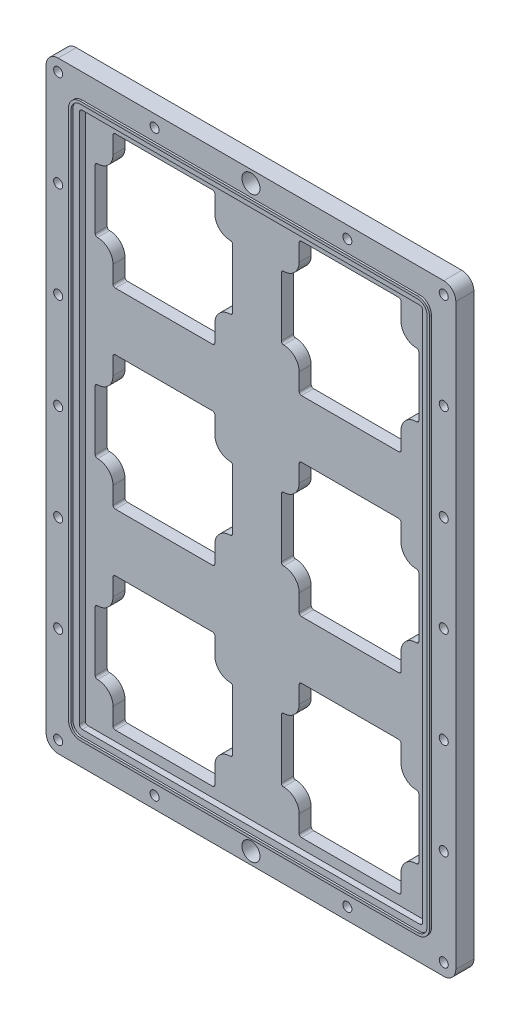
SolidWorks part; units mm, degrees
ref_plane "Front Plane" through (0, 0, 0) normal (0, 0, 1) x (1, 0, 0)
ref_plane "Top Plane" through (0, 0, 0) normal (0, 1, 0) x (1, 0, 0)
ref_plane "Right Plane" through (0, 0, 0) normal (1, 0, 0) x (0, 0, -1)
sketch "Sketch1" plane through (0, 0, 0) normal (0, 0, 1) x (1, 0, 0)
  line L1 (0, 0) -> (215.9, 0)
  line L2 (0, 0) -> (0, 317.5)
  line L3 (0, 317.5) -> (215.9, 317.5)
  line L4 (215.9, 0) -> (215.9, 317.5)
  dimension "D1" = 317.5
  dimension "D2" = 215.9
extrude "Boss-Extrude1" add sketch "Sketch1" along normal blind 9.525
sketch "Sketch4" plane through (0, 0, 9.525) normal (0, 0, 1) x (1, 0, 0)
  line L3 (0, 317.5) -> (0, 0) construction
  line L4 (6.35, 311.15) -> (209.55, 311.15) construction
  line L5 (6.35, 311.15) -> (6.35, 6.35) construction
  line L6 (6.35, 6.35) -> (209.55, 6.35) construction
  line L7 (209.55, 311.15) -> (209.55, 6.35) construction
  line L8 (215.9, 317.5) -> (0, 317.5) construction
  line L9 (215.9, 0) -> (215.9, 317.5) construction
  line L10 (0, 0) -> (215.9, 0) construction
  circle A0 centre (6.35, 6.35) radius 2.3813
  circle A1 centre (6.35, 311.15) radius 2.3813
  circle A2 centre (209.55, 311.15) radius 2.3813
  circle A3 centre (209.55, 6.35) radius 2.3813
  circle A4 centre (57.15, 311.15) radius 2.3813
  circle A5 centre (57.15, 6.35) radius 2.3812
  circle A6 centre (107.95, 311.15) radius 2.3813
  circle A7 centre (107.95, 6.35) radius 2.3813
  circle A8 centre (158.75, 311.15) radius 2.3813
  circle A9 centre (158.75, 6.35) radius 2.3813
  circle A10 centre (6.35, 260.35) radius 2.3813
  circle A11 centre (209.55, 260.35) radius 2.3813
  circle A12 centre (6.35, 209.55) radius 2.3813
  circle A13 centre (209.55, 209.55) radius 2.3813
  circle A14 centre (6.35, 158.75) radius 2.3812
  circle A15 centre (209.55, 158.75) radius 2.3813
  circle A16 centre (6.35, 107.95) radius 2.3812
  circle A17 centre (209.55, 107.95) radius 2.3813
  circle A18 centre (6.35, 57.15) radius 2.3813
  circle A19 centre (209.55, 57.15) radius 2.3813
  dimension "D5" = 4.7625
  dimension "D1" = 6.35
  dimension "D2" = 6.35
  dimension "D3" = 6.35
  dimension "D4" = 6.35
  dimension "D6" = 4
  dimension "D7" = 6
extrude "Cut-Extrude1" cut sketch "Sketch4" against normal through all
sketch "Sketch5" plane through (0, 0, 9.525) normal (0, 0, 1) x (1, 0, 0)
  line L0 (0, 317.5) -> (0, 0) construction
  line L1 (19.05, 304.8) -> (196.85, 304.8) construction
  line L2 (12.7, 298.45) -> (12.7, 19.05) construction
  line L3 (19.05, 12.7) -> (196.85, 12.7) construction
  line L4 (203.2, 298.45) -> (203.2, 19.05) construction
  line L5 (215.9, 317.5) -> (0, 317.5) construction
  line L6 (215.9, 0) -> (215.9, 317.5) construction
  line L7 (0, 0) -> (215.9, 0) construction
  line L8 (19.05, 14.2875) -> (196.85, 14.2875) construction
  line L9 (14.2875, 298.45) -> (14.2875, 19.05) construction
  line L10 (19.05, 303.2125) -> (196.85, 303.2125) construction
  line L11 (201.6125, 298.45) -> (201.6125, 19.05) construction
  line L12 (12.827, 298.45) -> (12.827, 19.05)
  line L13 (19.05, 304.673) -> (196.85, 304.673)
  line L14 (203.073, 298.45) -> (203.073, 19.05)
  line L15 (19.05, 12.827) -> (196.85, 12.827)
  line L16 (201.7395, 298.45) -> (201.7395, 19.05)
  line L17 (19.05, 303.3395) -> (196.85, 303.3395)
  line L18 (14.1605, 298.45) -> (14.1605, 19.05)
  line L19 (19.05, 14.1605) -> (196.85, 14.1605)
  arc A0 (196.85, 12.7) -> (203.2, 19.05) centre (196.85, 19.05) ccw construction
  arc A1 (12.7, 19.05) -> (19.05, 12.7) centre (19.05, 19.05) ccw construction
  arc A2 (196.85, 304.8) -> (203.2, 298.45) centre (196.85, 298.45) cw construction
  arc A3 (19.05, 304.8) -> (12.7, 298.45) centre (19.05, 298.45) ccw construction
  arc A4 (14.2875, 19.05) -> (19.05, 14.2875) centre (19.05, 19.05) ccw construction
  arc A5 (19.05, 303.2125) -> (14.2875, 298.45) centre (19.05, 298.45) ccw construction
  arc A6 (196.85, 303.2125) -> (201.6125, 298.45) centre (196.85, 298.45) cw construction
  arc A7 (196.85, 14.2875) -> (201.6125, 19.05) centre (196.85, 19.05) ccw construction
  arc A8 (19.05, 304.673) -> (12.827, 298.45) centre (19.05, 298.45) ccw
  arc A9 (196.85, 304.673) -> (203.073, 298.45) centre (196.85, 298.45) cw
  arc A10 (196.85, 12.827) -> (203.073, 19.05) centre (196.85, 19.05) ccw
  arc A11 (12.827, 19.05) -> (19.05, 12.827) centre (19.05, 19.05) ccw
  arc A12 (196.85, 303.3395) -> (201.7395, 298.45) centre (196.85, 298.45) cw
  arc A13 (19.05, 303.3395) -> (14.1605, 298.45) centre (19.05, 298.45) ccw
  arc A14 (14.1605, 19.05) -> (19.05, 14.1605) centre (19.05, 19.05) ccw
  arc A15 (196.85, 14.1605) -> (201.7395, 19.05) centre (196.85, 19.05) ccw
  dimension "D5" = 6.35
  dimension "D1" = 12.7
  dimension "D2" = 12.7
  dimension "D3" = 12.7
  dimension "D4" = 12.7
  dimension "D6" = 1.5875
  dimension "D7" = 1.5875
  dimension "D8" = 0.127
  dimension "D9" = 0.127
  dimension "D10" = 0.127
sketch "Sketch6" plane through (0, 0, 9.525) normal (0, 0, 1) x (1, 0, 0)
  line L24 (196.85, 300.0375) -> (19.05, 300.0375)
  line L25 (198.4375, 19.05) -> (198.4375, 298.45)
  line L26 (19.05, 17.4625) -> (196.85, 17.4625)
  line L27 (17.4625, 298.45) -> (17.4625, 19.05)
  line L28 (196.85, 300.0375) -> (19.05, 300.0375)
  line L29 (198.4375, 19.05) -> (198.4375, 298.45)
  line L30 (19.05, 17.4625) -> (196.85, 17.4625)
  line L31 (17.4625, 298.45) -> (17.4625, 19.05)
  arc A20 (19.05, 300.0375) -> (17.4625, 298.45) centre (19.05, 298.45) ccw
  arc A21 (198.4375, 298.45) -> (196.85, 300.0375) centre (196.85, 298.45) ccw
  arc A22 (196.85, 17.4625) -> (198.4375, 19.05) centre (196.85, 19.05) ccw
  arc A23 (17.4625, 19.05) -> (19.05, 17.4625) centre (19.05, 19.05) ccw
  arc A24 (19.05, 300.0375) -> (17.4625, 298.45) centre (19.05, 298.45) ccw
  arc A25 (198.4375, 298.45) -> (196.85, 300.0375) centre (196.85, 298.45) ccw
  arc A26 (196.85, 17.4625) -> (198.4375, 19.05) centre (196.85, 19.05) ccw
  arc A27 (17.4625, 19.05) -> (19.05, 17.4625) centre (19.05, 19.05) ccw
  dimension "D1" = 3.175
extrude "Cut-Extrude3" cut sketch "Sketch6" against normal blind 3.175
extrude "Boss-Extrude2" add sketch "Sketch5" along normal blind 1.016 contours L12 A11 L15 A10 L14 A9 L13 A8 A15 L19 A14 L18 A13 L17 A12 L16 region at (14.896, 302.604, 9.525)
sketch "Sketch7" plane through (0, 0, 9.525) normal (0, 0, 1) x (1, 0, 0)
  circle A0 centre (107.95, 6.35) radius 4.7625
  circle A1 centre (107.95, 311.15) radius 4.7625
  dimension "D1" = 9.525
extrude "Cut-Extrude4" cut sketch "Sketch7" against normal through all
fillet "Fillet1" radius 6.35 4 edges at (0, 317.5, 4.7625) (215.9, 317.5, 4.7625) (0, 0, 4.7625) (215.9, 0, 4.7625)
sketch "Sketch8" plane through (0, 0, 0) normal (0, 0, -1) x (-1, 0, 0)
  line L0 (-194.818, 275.209) -> (-194.818, 244.0178)
  line L1 (-185.42, 234.6198) -> (-185.42, 225.6282)
  line L2 (-182.6006, 222.8088) -> (-131.3942, 222.8088)
  line L3 (-128.5748, 225.6282) -> (-128.5748, 234.6198)
  line L4 (-119.1768, 244.0178) -> (-119.1768, 275.209)
  line L5 (-128.5748, 284.607) -> (-128.5748, 293.5986)
  line L6 (-131.3942, 296.418) -> (-182.6006, 296.418)
  line L7 (-185.42, 293.5986) -> (-185.42, 284.607)
  line L8 (-191.9986, 296.418) -> (-191.9986, 222.8088) construction
  line L9 (-194.818, 293.5986) -> (-119.1768, 293.5986) construction
  line L10 (-194.818, 296.418) -> (-119.1768, 296.418) construction
  line L11 (-194.818, 296.418) -> (-194.818, 222.8088) construction
  line L12 (-194.818, 222.8088) -> (-119.1768, 222.8088) construction
  line L13 (-119.1768, 296.418) -> (-119.1768, 222.8088) construction
  line L14 (-194.818, 284.607) -> (-119.1768, 284.607) construction
  line L15 (-194.818, 275.209) -> (-119.1768, 275.209) construction
  line L16 (-194.818, 244.0178) -> (-119.1768, 244.0178) construction
  line L17 (-194.818, 234.6198) -> (-119.1768, 234.6198) construction
  line L18 (-194.818, 225.6282) -> (-119.1768, 225.6282) construction
  line L19 (-185.42, 222.8088) -> (-185.42, 296.418) construction
  line L20 (-182.6006, 296.418) -> (-182.6006, 222.8088) construction
  line L21 (-131.3942, 296.418) -> (-131.3942, 222.8088) construction
  line L22 (-128.5748, 296.418) -> (-128.5748, 222.8088) construction
  line L23 (-121.9962, 222.8088) -> (-121.9962, 296.418) construction
  line L24 (-119.1768, 278.0284) -> (-194.818, 278.0284) construction
  line L27 (-131.3942, 298.45) -> (-182.6006, 298.45)
  line L28 (-187.452, 293.5986) -> (-187.452, 284.607)
  line L29 (-196.85, 275.209) -> (-196.85, 244.0178)
  line L30 (-187.452, 234.6198) -> (-187.452, 225.6282)
  line L31 (-182.6006, 220.7768) -> (-131.3942, 220.7768)
  line L32 (-126.5428, 225.6282) -> (-126.5428, 234.6198)
  line L33 (-117.1448, 244.0178) -> (-117.1448, 275.209)
  line L34 (-126.5428, 284.607) -> (-126.5428, 293.5986)
  line L35 (-209.55, 317.5) -> (-6.35, 317.5) construction
  line L36 (-215.9, 6.35) -> (-215.9, 311.15) construction
  arc A0 (-191.9986, 278.0284) -> (-185.42, 284.607) centre (-191.9986, 284.607) ccw
  arc A1 (-191.9986, 278.0284) -> (-194.818, 275.209) centre (-191.9986, 275.209) ccw
  arc A2 (-194.818, 244.0178) -> (-191.9986, 241.1984) centre (-191.9986, 244.0178) ccw
  arc A3 (-185.42, 234.6198) -> (-191.9986, 241.1984) centre (-191.9986, 234.6198) ccw
  arc A4 (-185.42, 225.6282) -> (-182.6006, 222.8088) centre (-182.6006, 225.6282) ccw
  arc A5 (-131.3942, 222.8088) -> (-128.5748, 225.6282) centre (-131.3942, 225.6282) ccw
  arc A6 (-121.9962, 241.1984) -> (-128.5748, 234.6198) centre (-121.9962, 234.6198) ccw
  arc A7 (-121.9962, 241.1984) -> (-119.1768, 244.0178) centre (-121.9962, 244.0178) ccw
  arc A8 (-119.1768, 275.209) -> (-121.9962, 278.0284) centre (-121.9962, 275.209) ccw
  arc A9 (-128.5748, 284.607) -> (-121.9962, 278.0284) centre (-121.9962, 284.607) ccw
  arc A10 (-128.5748, 293.5986) -> (-131.3942, 296.418) centre (-131.3942, 293.5986) ccw
  arc A11 (-182.6006, 296.418) -> (-185.42, 293.5986) centre (-182.6006, 293.5986) ccw
  arc A12 (-182.6006, 298.45) -> (-187.452, 293.5986) centre (-182.6006, 293.5986) ccw
  arc A13 (-191.9986, 280.0604) -> (-187.452, 284.607) centre (-191.9986, 284.607) ccw
  arc A14 (-191.9986, 280.0604) -> (-196.85, 275.209) centre (-191.9986, 275.209) ccw
  arc A15 (-196.85, 244.0178) -> (-191.9986, 239.1664) centre (-191.9986, 244.0178) ccw
  arc A16 (-187.452, 234.6198) -> (-191.9986, 239.1664) centre (-191.9986, 234.6198) ccw
  arc A17 (-187.452, 225.6282) -> (-182.6006, 220.7768) centre (-182.6006, 225.6282) ccw
  arc A18 (-131.3942, 220.7768) -> (-126.5428, 225.6282) centre (-131.3942, 225.6282) ccw
  arc A19 (-121.9962, 239.1664) -> (-126.5428, 234.6198) centre (-121.9962, 234.6198) ccw
  arc A20 (-121.9962, 239.1664) -> (-117.1448, 244.0178) centre (-121.9962, 244.0178) ccw
  arc A21 (-117.1448, 275.209) -> (-121.9962, 280.0604) centre (-121.9962, 275.209) ccw
  arc A22 (-126.5428, 284.607) -> (-121.9962, 280.0604) centre (-121.9962, 284.607) ccw
  arc A23 (-126.5428, 293.5986) -> (-131.3942, 298.45) centre (-131.3942, 293.5986) ccw
  dimension "D4" = 11.811
  dimension "D5" = 21.209
  dimension "D6" = 52.4002
  dimension "D1" = 73.6092
  dimension "D2" = 75.6412
  dimension "D3" = 2.8194
  dimension "D7" = 61.7982
  dimension "D8" = 70.7898
  dimension "D9" = 2.8194
  dimension "D10" = 9.398
  dimension "D11" = 12.2174
  dimension "D12" = 63.4238
  dimension "D13" = 66.2432
  dimension "D14" = 72.8218
  dimension "D15" = 55.2196
  dimension "D16" = 19.05
  dimension "D17" = 19.05
  dimension "D18" = 2.032
extrude "Cut-Extrude5" cut sketch "Sketch8" against normal blind 3.175
sketch "Sketch10" plane through (0, 0, 0) normal (0, 0, -1) x (-1, 0, 0)
  line L18 (-193.2305, 275.209) -> (-193.2305, 244.0178)
  line L19 (-183.8325, 234.6198) -> (-183.8325, 225.6282)
  line L20 (-182.6006, 224.3963) -> (-131.3942, 224.3963)
  line L21 (-130.1623, 225.6282) -> (-130.1623, 234.6198)
  line L22 (-120.7643, 244.0178) -> (-120.7643, 275.209)
  line L23 (-130.1623, 284.607) -> (-130.1623, 293.5986)
  line L24 (-131.3942, 294.8305) -> (-182.6006, 294.8305)
  line L25 (-183.8325, 293.5986) -> (-183.8325, 284.607)
  line L26 (-193.2305, 275.209) -> (-193.2305, 244.0178)
  line L27 (-183.8325, 234.6198) -> (-183.8325, 225.6282)
  line L28 (-182.6006, 224.3963) -> (-131.3942, 224.3963)
  line L29 (-130.1623, 225.6282) -> (-130.1623, 234.6198)
  line L30 (-120.7643, 244.0178) -> (-120.7643, 275.209)
  line L31 (-130.1623, 284.607) -> (-130.1623, 293.5986)
  line L32 (-131.3942, 294.8305) -> (-182.6006, 294.8305)
  line L33 (-183.8325, 293.5986) -> (-183.8325, 284.607)
  arc A28 (-191.9986, 276.4409) -> (-193.2305, 275.209) centre (-191.9986, 275.209) ccw
  arc A29 (-193.2305, 244.0178) -> (-191.9986, 242.7859) centre (-191.9986, 244.0178) ccw
  arc A30 (-183.8325, 234.6198) -> (-191.9986, 242.7859) centre (-191.9986, 234.6198) ccw
  arc A31 (-183.8325, 225.6282) -> (-182.6006, 224.3963) centre (-182.6006, 225.6282) ccw
  arc A32 (-131.3942, 224.3963) -> (-130.1623, 225.6282) centre (-131.3942, 225.6282) ccw
  arc A33 (-121.9962, 242.7859) -> (-130.1623, 234.6198) centre (-121.9962, 234.6198) ccw
  arc A34 (-121.9962, 242.7859) -> (-120.7643, 244.0178) centre (-121.9962, 244.0178) ccw
  arc A35 (-120.7643, 275.209) -> (-121.9962, 276.4409) centre (-121.9962, 275.209) ccw
  arc A36 (-130.1623, 284.607) -> (-121.9962, 276.4409) centre (-121.9962, 284.607) ccw
  arc A37 (-130.1623, 293.5986) -> (-131.3942, 294.8305) centre (-131.3942, 293.5986) ccw
  arc A38 (-182.6006, 294.8305) -> (-183.8325, 293.5986) centre (-182.6006, 293.5986) ccw
  arc A39 (-191.9986, 276.4409) -> (-183.8325, 284.607) centre (-191.9986, 284.607) ccw
  arc A40 (-191.9986, 276.4409) -> (-193.2305, 275.209) centre (-191.9986, 275.209) ccw
  arc A41 (-193.2305, 244.0178) -> (-191.9986, 242.7859) centre (-191.9986, 244.0178) ccw
  arc A42 (-183.8325, 234.6198) -> (-191.9986, 242.7859) centre (-191.9986, 234.6198) ccw
  arc A43 (-183.8325, 225.6282) -> (-182.6006, 224.3963) centre (-182.6006, 225.6282) ccw
  arc A44 (-131.3942, 224.3963) -> (-130.1623, 225.6282) centre (-131.3942, 225.6282) ccw
  arc A45 (-121.9962, 242.7859) -> (-130.1623, 234.6198) centre (-121.9962, 234.6198) ccw
  arc A46 (-121.9962, 242.7859) -> (-120.7643, 244.0178) centre (-121.9962, 244.0178) ccw
  arc A47 (-120.7643, 275.209) -> (-121.9962, 276.4409) centre (-121.9962, 275.209) ccw
  arc A48 (-130.1623, 284.607) -> (-121.9962, 276.4409) centre (-121.9962, 284.607) ccw
  arc A49 (-130.1623, 293.5986) -> (-131.3942, 294.8305) centre (-131.3942, 293.5986) ccw
  arc A50 (-182.6006, 294.8305) -> (-183.8325, 293.5986) centre (-182.6006, 293.5986) ccw
  arc A51 (-191.9986, 276.4409) -> (-183.8325, 284.607) centre (-191.9986, 284.607) ccw
  dimension "D1" = 1.5875
extrude "Cut-Extrude6" cut sketch "Sketch10" against normal through all
sketch "Sketch11" plane through (0, 0, 0) normal (0, 0, -1) x (-1, 0, 0)
  line L0 (-156.9974, 293.6494) -> (-156.9974, 298.45) construction
  line L1 (-191.9986, 293.6494) -> (-121.9962, 293.6494) construction
  line L2 (-191.9986, 293.6494) -> (-191.9986, 225.5774) construction
  line L3 (-191.9986, 225.5774) -> (-121.9962, 225.5774) construction
  line L4 (-121.9962, 293.6494) -> (-121.9962, 225.5774) construction
  line L5 (-131.3942, 298.45) -> (-182.6006, 298.45) construction
  line L6 (-156.9974, 225.5774) -> (-156.9974, 220.7768) construction
  line L7 (-182.6006, 220.7768) -> (-131.3942, 220.7768) construction
  line L8 (-191.9986, 259.6134) -> (-196.85, 259.6134) construction
  line L9 (-196.85, 275.209) -> (-196.85, 244.0178) construction
  line L10 (-121.9962, 259.6134) -> (-117.1448, 259.6134) construction
  line L11 (-117.1448, 244.0178) -> (-117.1448, 275.209) construction
  circle A0 centre (-191.9986, 293.6494) radius 1.3462
  circle A1 centre (-121.9962, 293.6494) radius 1.3462
  circle A2 centre (-121.9962, 225.5774) radius 1.3462
  circle A3 centre (-191.9986, 225.5774) radius 1.3462
  dimension "D3" = 2.6924
  dimension "D1" = 70.0024
  dimension "D2" = 68.072
extrude "Cut-Extrude7" cut sketch "Sketch11" against normal blind 4.7625
pattern_linear "LPattern1" count 2 spacing 98.0948 along (-1, 0, 0) count 3 spacing 100.8634 along (0, -1, 0) of "Cut-Extrude6", "Cut-Extrude5", "Cut-Extrude7"
